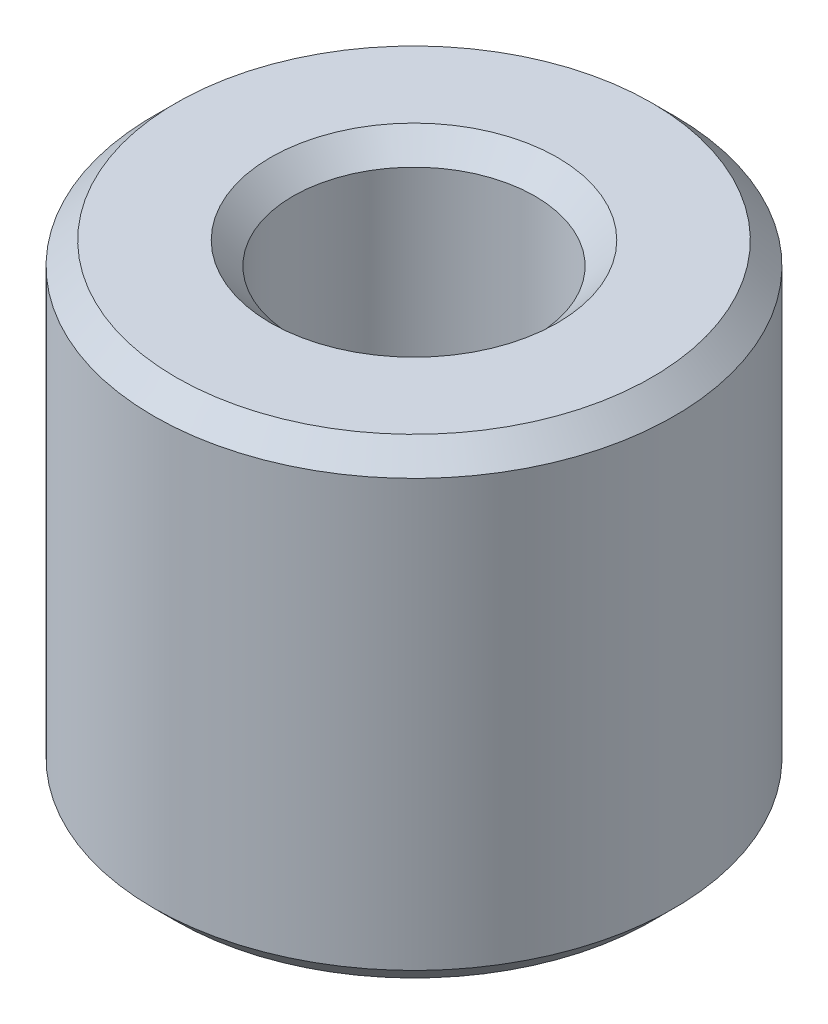
SolidWorks part; units mm, degrees
ref_plane "Front Plane" through (0, 0, 0) normal (0, 0, 1) x (1, 0, 0)
ref_plane "Top Plane" through (0, 0, 0) normal (0, 1, 0) x (1, 0, 0)
ref_plane "Right Plane" through (0, 0, 0) normal (1, 0, 0) x (0, 0, -1)
sketch "Sketch1" plane through (0, 0, 0) normal (0, 1, 0) x (1, 0, 0)
  circle A0 centre (0, 0) radius 45
  dimension "SLEEVE_OD" = 90
extrude "Boss-Extrude1" add sketch "Sketch1" along normal blind 81.4324
sketch "Sketch2" plane through (0, 0, 0) normal (0, 1, 0) x (1, 0, 0)
  circle A0 centre (0, 0) radius 20.9301
  dimension "BORE_D" = 41.8602
extrude "Cut-Extrude1" cut sketch "Sketch2" along normal through all
chamfer "Chamfer1" distance 3.8688 angle 45 4 edges at (0, 81.4324, 20.9301) (0, 0, 20.9301) (0, 0, 45) (0, 81.4324, 45)
